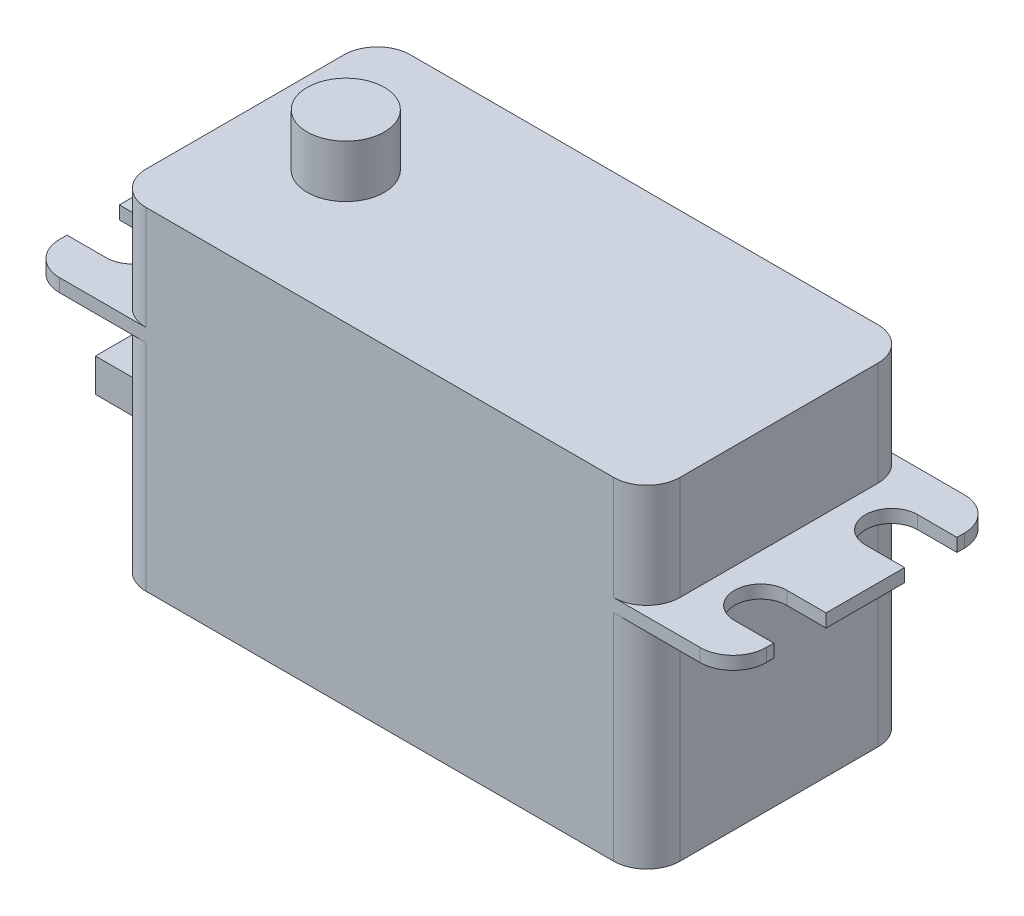
SolidWorks part; units mm, degrees
ref_plane "Front Plane" through (0, 0, 0) normal (0, 0, 1) x (1, 0, 0)
ref_plane "Top Plane" through (0, 0, 0) normal (0, 1, 0) x (1, 0, 0)
ref_plane "Right Plane" through (0, 0, 0) normal (1, 0, 0) x (0, 0, -1)
sketch "Sketch1" plane through (0, 0, 0) normal (0, 1, 0) x (1, 0, 0)
  line L0 (-16.17, 0) -> (16.17, 0) construction
  line L1 (-24.46, -10.1) -> (24.46, -10.1)
  line L2 (-27, -7.56) -> (-27, 7.56)
  line L3 (-24.46, 10.1) -> (24.46, 10.1)
  line L4 (27, -7.56) -> (27, 7.56)
  line L5 (-27, -10.1) -> (27, 10.1) construction
  line L6 (-27, 10.1) -> (27, -10.1) construction
  line L7 (0, -11.11) -> (0, 11.11) construction
  line L8 (24, 3) -> (27, 3)
  line L9 (24, 7) -> (27, 7)
  line L10 (27, 7) -> (27, 3)
  line L11 (24, -3) -> (27, -3)
  line L12 (24, -7) -> (27, -7)
  line L13 (27, -7) -> (27, -3)
  line L14 (-24, 7) -> (-27, 7)
  line L15 (-24, 3) -> (-27, 3)
  line L16 (-27, 3) -> (-27, 7)
  line L17 (-24, -7) -> (-27, -7)
  line L18 (-24, -3) -> (-27, -3)
  line L19 (-27, -3) -> (-27, -7)
  arc A0 (24, 7) -> (24, 3) centre (24, 5) ccw
  arc A1 (24, -7) -> (24, -3) centre (24, -5) cw
  arc A2 (-24, -7) -> (-24, -3) centre (-24, -5) ccw
  arc A3 (-24, 7) -> (-24, 3) centre (-24, 5) cw
  arc A4 (-24.46, -10.1) -> (-27, -7.56) centre (-24.46, -7.56) cw
  arc A5 (24.46, -10.1) -> (27, -7.56) centre (24.46, -7.56) ccw
  arc A6 (24.46, 10.1) -> (27, 7.56) centre (24.46, 7.56) cw
  arc A7 (-27, 7.56) -> (-24.46, 10.1) centre (-24.46, 7.56) cw
  point P0 (0, 0)
  dimension "D3" = 4
  dimension "D6" = 2.54
  dimension "D1" = 54
  dimension "D2" = 20.2
  dimension "D4" = 48
  dimension "D5" = 10
extrude "Boss-Extrude1" add sketch "Sketch1" along normal blind 1 contours A7 L2 L14 A3 L15 L18 A2 L17 A4 L1 A5 L4 L12 A1 L11 L8 A0 L9 A6 L3 region at (0, 0, 0)
sketch "Sketch3" plane through (0, 1, 0) normal (0, 1, 0) x (1, 0, 0)
  line L1 (-17.86, -10.1) -> (17.86, -10.1)
  line L2 (-20.4, -7.56) -> (-20.4, 7.56)
  line L3 (-17.86, 10.1) -> (17.86, 10.1)
  line L4 (20.4, -7.56) -> (20.4, 7.56)
  line L5 (-20.4, -10.1) -> (20.4, 10.1) construction
  line L6 (-20.4, 10.1) -> (20.4, -10.1) construction
  arc A0 (-17.86, -10.1) -> (-20.4, -7.56) centre (-17.86, -7.56) cw
  arc A1 (17.86, -10.1) -> (20.4, -7.56) centre (17.86, -7.56) ccw
  arc A2 (17.86, 10.1) -> (20.4, 7.56) centre (17.86, 7.56) cw
  arc A3 (-20.4, 7.56) -> (-17.86, 10.1) centre (-17.86, 7.56) cw
  point P0 (0, 0)
  dimension "D3" = 2.54
  dimension "D1" = 40.8
  dimension "D2" = 20.2
extrude "Boss-Extrude2" add sketch "Sketch3" along normal blind 7.95
sketch "Sketch4" plane through (0, 0, 0) normal (0, -1, 0) x (1, 0, 0)
  line L1 (-17.86, -10.1) -> (17.86, -10.1)
  line L2 (-20.4, -7.56) -> (-20.4, 7.56)
  line L3 (-17.86, 10.1) -> (17.86, 10.1)
  line L4 (20.4, -7.56) -> (20.4, 7.56)
  line L5 (-20.4, -10.1) -> (20.4, 10.1) construction
  line L6 (-20.4, 10.1) -> (20.4, -10.1) construction
  arc A0 (-17.86, -10.1) -> (-20.4, -7.56) centre (-17.86, -7.56) cw
  arc A1 (17.86, -10.1) -> (20.4, -7.56) centre (17.86, -7.56) ccw
  arc A2 (17.86, 10.1) -> (20.4, 7.56) centre (17.86, 7.56) cw
  arc A3 (-20.4, 7.56) -> (-17.86, 10.1) centre (-17.86, 7.56) cw
  point P0 (0, 0)
  dimension "D3" = 2.54
  dimension "D1" = 20.2
  dimension "D2" = 40.8
extrude "Boss-Extrude3" add sketch "Sketch4" along normal blind 16.45
sketch "Sketch5" plane through (-20.4, 0, 0) normal (-1, 0, 0) x (0, 0, 1)
  line L0 (-0.8843, -9.5287) -> (-0.8843, -11.2259)
  line L1 (-3.81, -11.6473) -> (3.81, -11.6473)
  line L2 (-3.81, -11.6473) -> (-3.81, -9.1073)
  line L3 (-3.81, -9.1073) -> (3.81, -9.1073)
  line L4 (3.81, -11.6473) -> (3.81, -9.1073)
  line L5 (-3.4243, -9.5287) -> (-1.6557, -9.5287)
  line L6 (-3.4243, -9.5287) -> (-3.4243, -11.2259)
  line L7 (-3.4243, -11.2259) -> (-1.6557, -11.2259)
  line L8 (-1.6557, -9.5287) -> (-1.6557, -11.2259)
  line L9 (-0.8843, -9.5287) -> (0.8843, -9.5287)
  line L10 (0.8843, -9.5287) -> (0.8843, -11.2259)
  line L11 (-0.8843, -11.2259) -> (0.8843, -11.2259)
  line L12 (1.6557, -9.5287) -> (1.6557, -11.2259)
  line L13 (1.6557, -9.5287) -> (3.4243, -9.5287)
  line L14 (3.4243, -9.5287) -> (3.4243, -11.2259)
  line L15 (1.6557, -11.2259) -> (3.4243, -11.2259)
  point P8 (0, -11.6473)
  point P18 (-3.4243, -10.3773)
  point P19 (-3.81, -10.3773)
  point P20 (0, -11.2259)
  dimension "D2" = 2.54
  dimension "D3" = 2.54
  dimension "D4" = 7.62
  dimension "D1" = 3
extrude "Boss-Extrude4" add sketch "Sketch5" along normal blind 7.62
sketch "Sketch6" plane through (0, 8.95, 0) normal (0, 1, 0) x (1, 0, 0)
  circle A0 centre (-12.7, 0) radius 2.95
  dimension "D1" = 5.9
  dimension "D2" = 12.7
extrude "Boss-Extrude5" add sketch "Sketch6" along normal blind 4
other "CPoint1" parameters "Diameter"=25.4, "StubLength"=38.1
ref_axis "Axis1" through (-38.02, -11.2259, -3.4243) along (1, 0, 0)
other "CPoint2" parameters "Diameter"=25.4, "StubLength"=38.1
ref_axis "Axis2" through (-38.02, -11.2259, -0.8843) along (1, 0, 0)
other "CPoint3" parameters "Diameter"=25.4, "StubLength"=38.1
ref_axis "Axis3" through (-38.02, -11.2259, 1.6557) along (1, 0, 0)
equation "\"Bodytube_OD\" = 6.17in"
equation "\"Bodytube_ID\" = 5.998in"
equation "\"Motor_OD\" = 4in"
equation "\"Fwd_Tube_Length\" = 40in"
equation "\"Mid_Tube_Length\" = 1in"
equation "\"Aft_Section_Length\"= 39in"
equation "\"AB_Coupler_OD_Length\"= 1in"
equation "\"AB_Coupling_Section_Length\"= 0.375in"
equation "\"AB_Coupler_Length\"= \"AB_Coupler_OD_Length\" + \"AB_Coupling_Section_Length\" * 2"
equation "\"Cutout_Angle\" = 80"
equation "\"AB_Paddle_Height\" = 0.375in"
equation "\"AB_Coupler_Num_Screws\"= 4"
equation "\"Num_Cutouts\" = 3"
equation "\"AB_Coupler_OD\"= 6.17in"
equation "\"AB_Coupler_ID\"= 5.75in"
equation "\"AB_Coupler_Surface_Diameter\"= 5.998in"
equation "\"AB_Coupling_Screw_Diameter\"= 0.15748in"
equation "\"AB_Central_Bushing_Length\" = .4724in"
equation "\"Lead_Screw_Dist\" = 3.4in"
equation "\"Lead_Screw_Diam\" = 0.386in"
equation "\"Paddle_Pin_Offset\" = .25in"
equation "\"Paddle_Pin_Radius\" = 2.25in"
equation "\"Paddle_Gear_OD\" = 3.2in"
equation "\"Drive_Gear_OD\" = 1.7in"
equation "\"Fwd_BKHD_From_Top\" = 18in"
equation "\"Fin_Thickness\"= .118in"
equation "\"Guiderail_Cutout_Diameter\"= 1.5in"
equation "\"DB9_Hole_Dist\" = 25mm"
equation "\"Airbrakes_Wire_Hole_Dia\" = .25in"
equation "\"Airbrakes_Wire_Hole_Dist\" = 1.1in"
equation "\"Servo_Gear_Offset\" = 0.5in"
equation "\"D2@Sketch6\"=\"Servo_Gear_Offset\""
